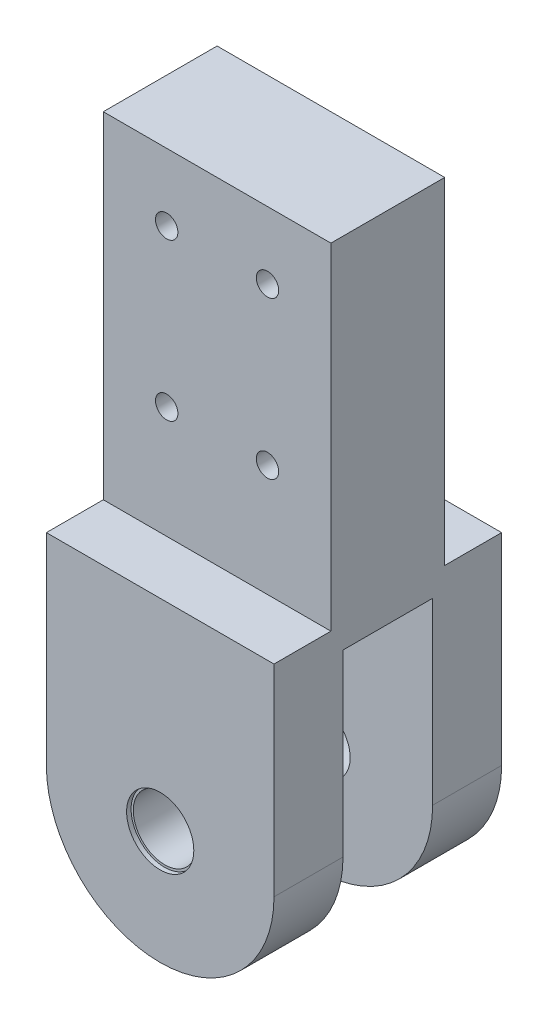
SolidWorks part; units mm, degrees
ref_plane "Front Plane" through (0, 0, 0) normal (0, 0, 1) x (1, 0, 0)
ref_plane "Top Plane" through (0, 0, 0) normal (0, 1, 0) x (1, 0, 0)
ref_plane "Right Plane" through (0, 0, 0) normal (1, 0, 0) x (0, 0, -1)
sketch "Sketch1" plane through (0, 0, 0) normal (0, 0, 1) x (1, 0, 0)
  line L0 (-25.4, 0) -> (-25.4, 120)
  line L1 (-25.4, 120) -> (25.4, 120)
  line L2 (25.4, 120) -> (25.4, 0)
  line L4 (-11.25, 105) -> (11.25, 105) construction
  line L5 (-11.25, 105) -> (-11.25, 70) construction
  line L6 (-11.25, 70) -> (11.25, 70) construction
  line L7 (11.25, 105) -> (11.25, 70) construction
  circle A0 centre (0, 0) radius 7
  arc A1 (-25.4, 0) -> (25.4, 0) centre (0, 0) ccw
  circle A2 centre (-11.25, 105) radius 2.5
  circle A3 centre (11.25, 105) radius 2.5
  circle A4 centre (11.25, 70) radius 2.5
  circle A5 centre (-11.25, 70) radius 2.5
  point P13 (0, 70)
  dimension "D1" = 14
  dimension "D4" = 5
  dimension "D2" = 50.8
  dimension "D3" = 120
  dimension "D5" = 35
  dimension "D6" = 15
  dimension "D7" = 22.5
extrude "Boss-Extrude1" add sketch "Sketch1" along normal mid plane 50.8
sketch "Sketch2" plane through (25.4, 0, 0) normal (1, 0, 0) x (0, 0, -1)
  line L0 (-25.4, -25.4) -> (25.4, -25.4) construction
  line L1 (-10, 40) -> (10, 40)
  line L2 (-10, 40) -> (-10, -25.4)
  line L3 (-10, -25.4) -> (10, -25.4)
  line L4 (10, 40) -> (10, -25.4)
  line L5 (-25.4, 0) -> (25.4, 0) construction
  point P8 (0, 0)
  point P9 (0, 40)
  dimension "D1" = 20
  dimension "D2" = 40
extrude "Cut-Extrude1" cut sketch "Sketch2" against normal through all
sketch "Sketch3" plane through (0, 0, 25.4) normal (0, 0, 1) x (1, 0, 0)
  circle A0 centre (0, 0) radius 7.5
  dimension "D1" = 15
extrude "Cut-Extrude2" cut sketch "Sketch3" against normal blind 1
sketch "Sketch4" plane through (0, 0, -25.4) normal (0, 0, -1) x (-1, 0, 0)
  circle A0 centre (0, 0) radius 7.5
  dimension "D1" = 15
extrude "Cut-Extrude3" cut sketch "Sketch4" against normal blind 1
sketch "Sketch6" plane through (25.4, 0, 0) normal (1, 0, 0) x (0, 0, -1)
  line L1 (-25.4, 120) -> (-12.7, 120)
  line L2 (-25.4, 120) -> (-25.4, 45)
  line L3 (-25.4, 45) -> (-12.7, 45)
  line L4 (-12.7, 120) -> (-12.7, 45)
  line L5 (25.4, 120) -> (12.7, 120)
  line L6 (25.4, 120) -> (25.4, 45)
  line L7 (25.4, 45) -> (12.7, 45)
  line L8 (12.7, 120) -> (12.7, 45)
  dimension "D1" = 25.4
  dimension "D2" = 75
extrude "Cut-Extrude4" cut sketch "Sketch6" against normal through all
